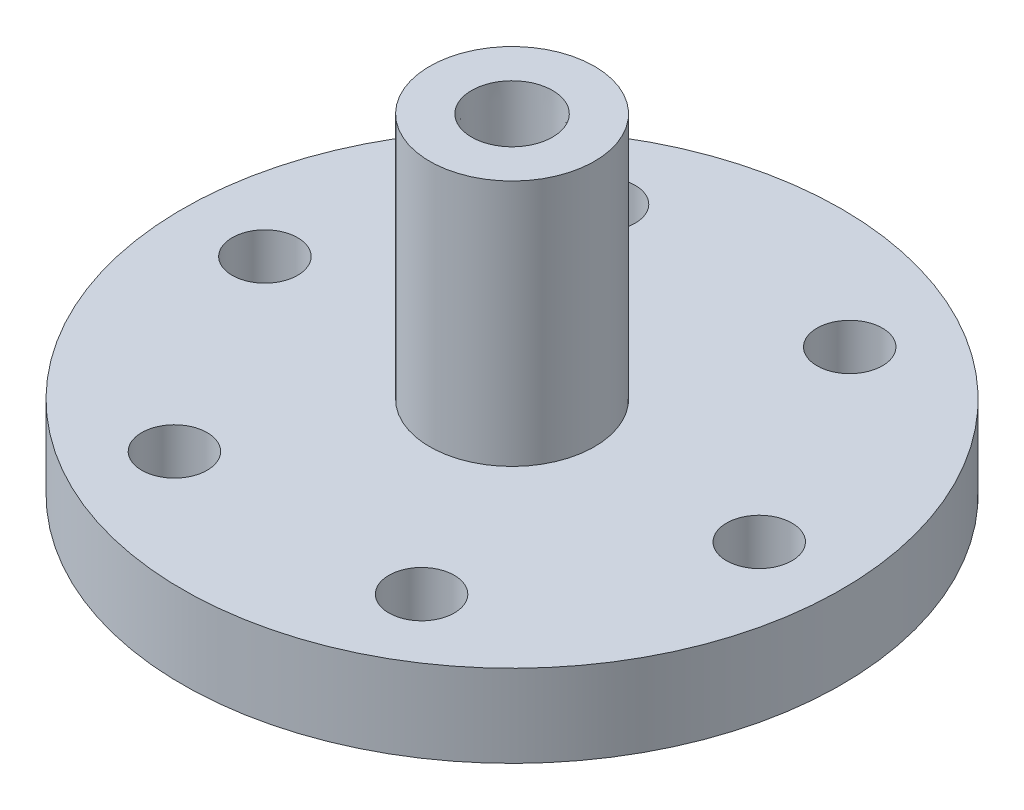
SolidWorks part; units mm, degrees
ref_plane "Front Plane" through (0, 0, 0) normal (0, 0, 1) x (1, 0, 0)
ref_plane "Top Plane" through (0, 0, 0) normal (0, 1, 0) x (1, 0, 0)
ref_plane "Right Plane" through (0, 0, 0) normal (1, 0, 0) x (0, 0, -1)
ref_axis "Axis1" through (0, 29.6, 0) along (0, -1, 0)
sketch "Sketch1" plane through (0, 0, 0) normal (0, 0, 1) x (1, 0, 0)
  line L0 (0, 0) -> (-12.7, 0)
  line L1 (-12.7, 0) -> (-12.7, -38.1)
  line L2 (-12.7, -38.1) -> (-50.8, -38.1)
  line L3 (-50.8, -38.1) -> (-50.8, -50.8)
  line L4 (-50.8, -50.8) -> (-13.081, -50.8)
  line L5 (0, -50.8) -> (0, 0)
  line L6 (0, -50.8) -> (-9.525, -50.8)
  line L7 (-9.525, -50.8) -> (-9.525, -48.26)
  line L8 (-9.525, -48.26) -> (-13.081, -48.26)
  line L9 (-13.081, -48.26) -> (-13.081, -50.8)
  dimension "D1" = 12.7
  dimension "D2" = 50.8
  dimension "D3" = 50.8
  dimension "D4" = 12.7
  dimension "D5" = 9.525
  dimension "D6" = 3.556
  dimension "D7" = 2.54
revolve "Revolve1" add sketch "Sketch1" angle 360 about L5
hole_wizard "1/4 NPT Tapped Hole1" positions "Sketch2" profile "Sketch4" size "1/4" standard "ANSI Inch" end condition through all
sketch "Sketch2" plane through (0, 0, 0) normal (0, 1, 0) x (1, 0, 0)
  point P0 (0, 0)
cosmetic thread "Hole Thread1" parameters "D1"=9.906, "D2"=13.7092
sketch "Sketch4" plane through (0, 0, 0) normal (1, 0, 0) x (0, 0, 1)
  line L0 (0, 0) -> (0, 50.8)
  line L1 (0, 50.8) -> (5.5626, 50.8)
  line L2 (-5.9437, 9.906) -> (-6.2403, 0) construction
  line L3 (5.5626, 50.8) -> (5.5626, 9.906)
  line L4 (5.5626, 9.906) -> (5.9437, 9.906)
  line L5 (5.9437, 9.906) -> (6.2403, 0)
  line L7 (6.2403, 0) -> (0, 0)
  line L8 (0, -6.35) -> (0, 107.95) construction
  line L11 (-5.5626, 9.906) -> (-5.9437, 9.906) construction
  dimension "Thru Tap Drill Dia." = 11.1252
  dimension "Thru Tap Drill Depth" = 50.8
  dimension "Thread Dia." = 12.4806
  dimension "Thread Angle" = 3.43
  dimension "Thread Depth" = 9.906
hole_wizard "3/8 Clearance Hole1" positions "Sketch5" profile "Sketch6" hole size "3/8" standard "ANSI Inch" end condition through all
sketch "Sketch5" plane through (0, -38.1, 0) normal (0, 1, 0) x (1, 0, 0)
  point P0 (38.1, 0)
  dimension "D1" = 38.1
sketch "Sketch6" plane through (38.1, -38.1, 0) normal (1, 0, 0) x (0, 0, 1)
  line L0 (0, 0) -> (0, 12.7)
  line L1 (0, 12.7) -> (5.0419, 12.7)
  line L2 (5.0419, 12.7) -> (5.0419, 0)
  line L5 (5.0419, 0) -> (0, 0)
  line L11 (0, -6.35) -> (0, 107.95) construction
  dimension "Thru Hole Dia." = 10.0838
  dimension "Thru Hole Depth" = 12.7
pattern_circular "CirPattern1" count 6 over 360 about axis through (0, 29.6, 0) along (0, -1, 0) of "3/8 Clearance Hole1"
ref_plane "Plane2" through (-43.9941, 0, 25.4) normal (-0.866, 0, 0.5) x (0, -1, 0)
hole_wizard "1/32 (0.03125) Diameter Hole1" positions "Sketch8" profile "Sketch9" hole size "1/32" standard "ANSI Inch" end condition up to next
sketch "Sketch8" plane through (-43.9941, 0, 25.4) normal (-0.866, 0, 0.5) x (0, -1, 0)
  line L0 (-29.6, 0) -> (80.4, 0) construction
  line L1 (50.8, -50.8) -> (50.8, 50.8) construction
  point P0 (44.45, 0)
  dimension "D1" = 6.35
sketch "Sketch9" plane through (-43.9941, -44.45, 25.4) normal (0, 1, 0) x (0.5, 0, 0.866)
  line L0 (0, 0) -> (0, 45.2374)
  line L1 (0, 45.2374) -> (0.3969, 45.2374)
  line L2 (0.3969, 45.2374) -> (0.3969, 0)
  line L5 (0.3969, 0) -> (0, 0)
  line L11 (0, -6.35) -> (0, 107.95) construction
  dimension "Thru Hole Dia." = 0.7937
  dimension "Thru Hole Depth" = 45.2374
hole_wizard "1/4 (0.25) Diameter Hole1" positions "Sketch10" profile "Sketch11" hole size "1/4" standard "ANSI Inch"
sketch "Sketch10" plane through (-43.9941, 0, 25.4) normal (-0.866, 0, 0.5) x (0, -1, 0)
  line L0 (-29.6, 0) -> (80.4, 0) construction
  point P0 (44.45, 0)
sketch "Sketch11" plane through (-43.9941, -44.45, 25.4) normal (0, 1, 0) x (0.5, 0, 0.866)
  line L0 (0, 0) -> (0, 14.6077)
  line L1 (0, 14.6077) -> (3.175, 12.7)
  line L2 (3.175, 12.7) -> (3.175, 0)
  line L5 (3.175, 0) -> (0, 0)
  line L10 (0, 14.6077) -> (-3.175, 12.7) construction
  line L11 (0, -6.35) -> (0, 107.95) construction
  dimension "Hole Dia." = 6.35
  dimension "Hole Depth" = 12.7
  dimension "Drill Angle" = 118
